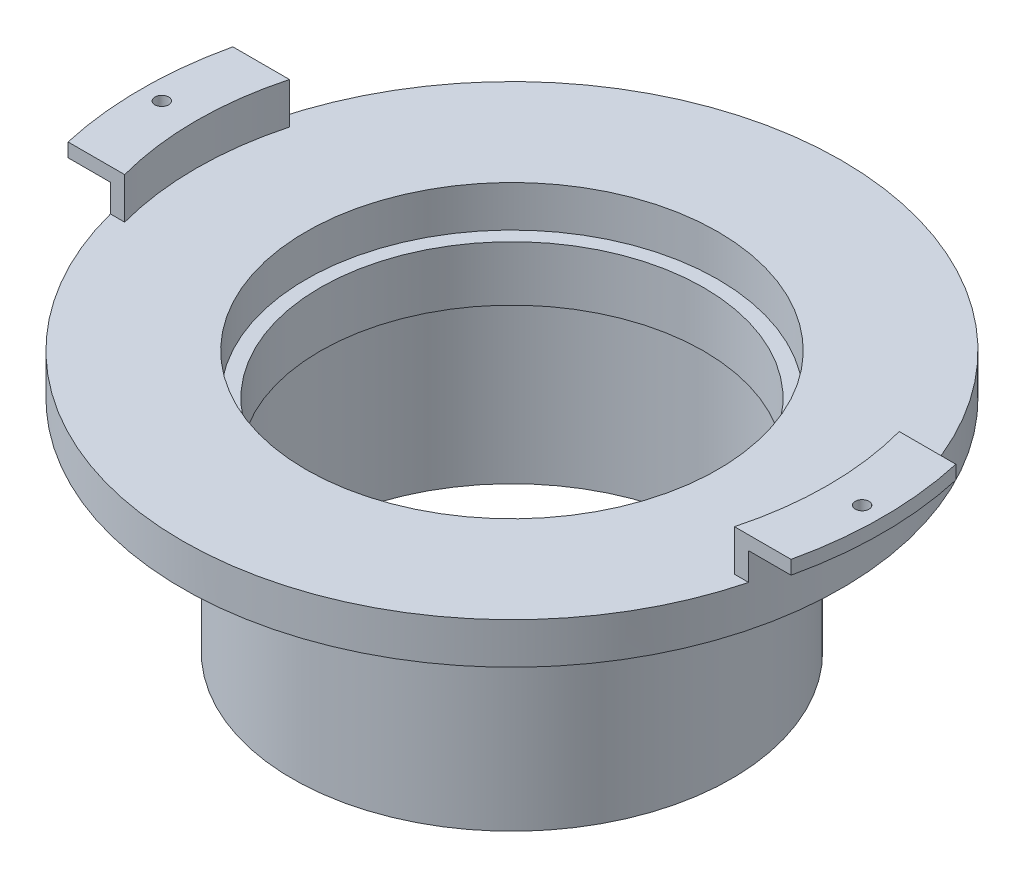
SolidWorks part; units mm, degrees
ref_plane "Front Plane" through (0, 0, 0) normal (0, 0, 1) x (1, 0, 0)
ref_plane "Top Plane" through (0, 0, 0) normal (0, 1, 0) x (1, 0, 0)
ref_plane "Right Plane" through (0, 0, 0) normal (1, 0, 0) x (0, 0, -1)
sketch "Sketch1" plane through (0, 0, 0) normal (0, 0, 1) x (1, 0, 0)
  line L0 (-80, -95) -> (-80, -15)
  line L25 (-80, -15) -> (-120, -15)
  line L26 (-120, -15) -> (-120, 10)
  line L27 (-120, 10) -> (-135, 10)
  line L28 (-135, 10) -> (-135, 15)
  line L29 (-135, 15) -> (-115, 15)
  line L30 (-115, 15) -> (-115, 0)
  line L31 (-115, 0) -> (-75, 0)
  line L32 (-69.8, -15) -> (-69.8, -35)
  line L33 (-69.8, -35) -> (-72.8, -35)
  line L34 (-72.8, -35) -> (-72.8, -25)
  line L35 (-72.8, -25) -> (-75, -25)
  line L36 (-75, -25) -> (-75, -95)
  line L37 (-75, -95) -> (-80, -95)
  line L41 (-69.8, -15) -> (-75, -15)
  line L42 (-75, 0) -> (-75, -15)
  dimension "D1" = 2.2
  dimension "D2" = 3
  dimension "D3" = 5
  dimension "D5" = 25
  dimension "D6" = 15
  dimension "D7" = 15
  dimension "D8" = 5
  dimension "D9" = 75
  dimension "D10" = 80
  dimension "D11" = 20
  dimension "D12" = 5
  dimension "D13" = 40
ref_axis "Axis1" through (0, -100.5, 0) along (0, 1, 0)
revolve "Revolve1" add sketch "Sketch1" angle 360 about axis through (0, -100.5, 0) along (0, 1, 0)
sketch "Sketch2" plane through (0, 10, 0) normal (0, -1, 0) x (1, 0, 0)
  circle A0 centre (127.5, 0) radius 2.5
  circle A1 centre (-127.5, 0) radius 2.5
  circle A2 centre (0, 0) radius 120 construction
  dimension "D1" = 5
  dimension "D3" = 127.5
  dimension "D2" = 127.5
extrude "Cut-Extrude3" cut sketch "Sketch2" against normal up to surface (5 mm away) up to face at (0, 15, -135)
sketch "Sketch3" plane through (0, 15, 0) normal (0, 1, 0) x (1, 0, 0)
  line L0 (-111.018, -30) -> (-131.6245, -30)
  line L1 (131.6245, -30) -> (111.018, -30)
  line L5 (131.6245, 30) -> (111.018, 30)
  line L9 (-111.018, 30) -> (-131.6245, 30)
  circle A0 centre (0, 0) radius 135 construction
  circle A1 centre (-127.5, 0) radius 2.5 construction
  arc A2 (-131.6245, -30) -> (131.6245, -30) centre (0, 0) ccw
  circle A3 centre (0, 0) radius 115 construction
  arc A4 (-111.018, -30) -> (111.018, -30) centre (0, 0) ccw
  arc A5 (111.018, 30) -> (-111.018, 30) centre (0, 0) ccw
  arc A6 (131.6245, 30) -> (-131.6245, 30) centre (0, 0) ccw
  point P6 (0, 0)
  dimension "D2" = 30
  dimension "D1" = 30
extrude "Cut-Extrude4" cut sketch "Sketch3" against normal up to surface (15 mm away) up to face at (0, 0, -115)
